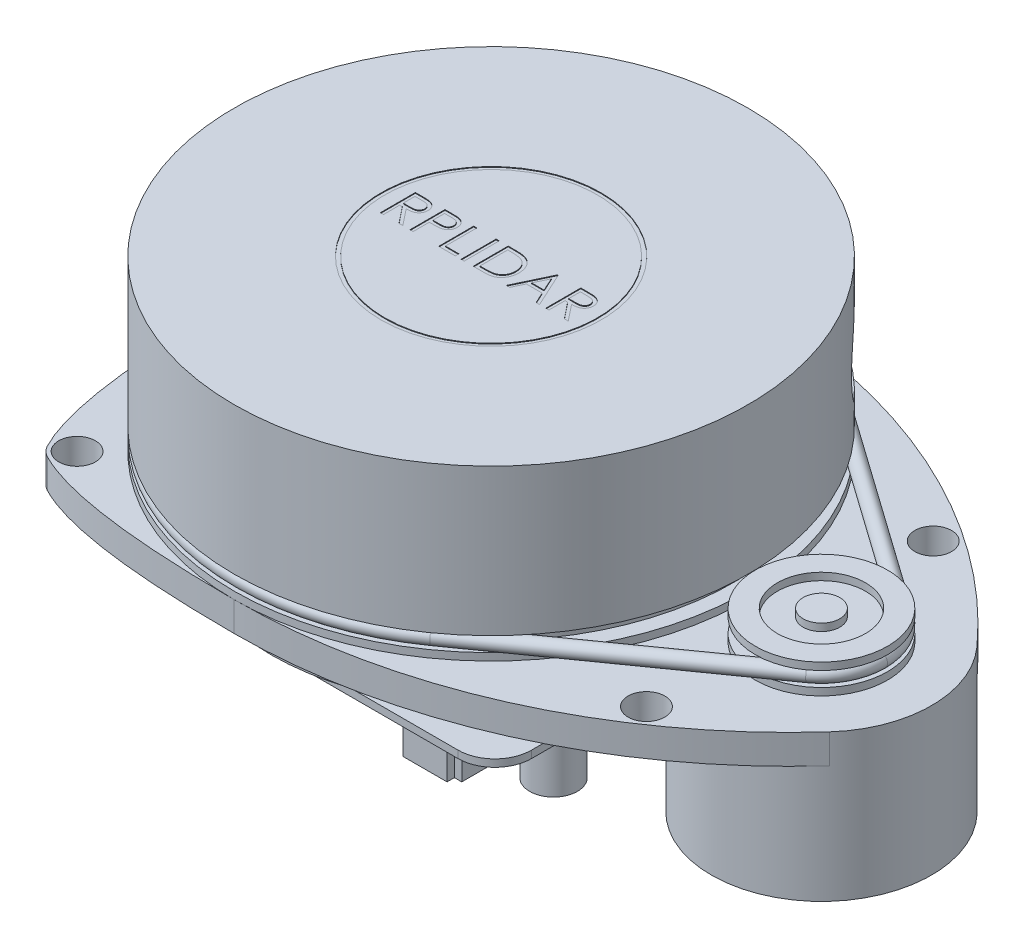
SolidWorks part; units mm, degrees
ref_plane "Front Plane" through (0, 0, 0) normal (0, 0, 1) x (1, 0, 0)
ref_plane "Top Plane" through (0, 0, 0) normal (0, 1, 0) x (1, 0, 0)
ref_plane "Right Plane" through (0, 0, 0) normal (1, 0, 0) x (0, 0, -1)
sketch "Sketch1" plane through (0, 0, 0) normal (0, 0, 1) x (1, 0, 0)
  line L0 (0, 67.5294) -> (0, -49.4672) construction
  line L1 (0, 0) -> (-35, 0)
  line L2 (38.5, 0) -> (-38.5, 0) construction
  line L3 (-35, 0) -> (-35, 1)
  line L4 (-35, 1) -> (-33, 1)
  line L5 (-33, 1) -> (-33, 3)
  line L6 (-33, 3) -> (-35, 3)
  line L7 (-35, 3) -> (-35, 23)
  line L8 (0, 23) -> (0, 0)
  line L9 (-15, 23) -> (-15, 22.9)
  line L10 (-15, 22.9) -> (-14.5, 22.9)
  line L11 (-14.5, 22.9) -> (-14.5, 23)
  line L12 (-35, 23) -> (-15, 23)
  line L13 (-14.5, 23) -> (0, 23)
  dimension "D1" = 1
  dimension "D2" = 2
  dimension "D3" = 2
  dimension "D4" = 35
  dimension "D5" = 2
  dimension "D6" = 23
  dimension "D7" = 0.1
  dimension "D8" = 0.5
  dimension "D9" = 14.5
revolve "Revolve2" add sketch "Sketch1" angle 360 about L0
sketch "Sketch2" plane through (0, 23, 0) normal (0, 1, 0) x (1, 0, 0)
  text T0 "RPLIDAR" font "Century Gothic" height in points 18
  dimension "D1" = 2.3813
extrude "Cut-Extrude2" cut sketch "Sketch2" against normal blind 0.1
sketch "Sketch3" plane through (0, 1, 0) normal (0, 1, 0) x (1, 0, 0)
  line L0 (-51.4402, 0) -> (173.1842, 0) construction
  line L1 (20.2222, 28.5668) -> (50.2, 7.3457)
  line L2 (50.2, -7.3457) -> (20.2222, -28.5668)
  circle A0 centre (0, 0) radius 35 construction
  arc A1 (20.2222, 28.5668) -> (20.2222, -28.5668) centre (0, 0) ccw
  arc A2 (50.2, -7.3457) -> (50.2, 7.3457) centre (45, 0) ccw
  circle A3 centre (0, 0) radius 35 construction
  dimension "D2" = 18
  dimension "D1" = 45
sketch "Sketch4" plane through (0, 0, 0) normal (0, 0, 1) x (1, 0, 0)
  line L0 (54, 2) -> (54, 1) construction
  line L1 (54, 1) -> (50.2, 1) construction
  line L3 (-51.4402, 1) -> (173.1842, 1) construction
  line L4 (54, 2) -> (53, 2) construction
  circle A0 centre (53, 2) radius 1
  point P5 (54, 1)
  dimension "D3" = 2
  dimension "D1" = 1
  dimension "D2" = 1
sweep "Sweep1" add profiles "Sketch4" path "Sketch3"
sketch "Sketch11" plane through (0, 0, 0) normal (0, 1, 0) x (1, 0, 0)
  circle A6 centre (45, 0) radius 9
  arc A7 (54, 0) -> (50.2, 7.3457) centre (45, 0) ccw construction
extrude "Boss-Extrude2" add sketch "Sketch11" along normal blind 1 separate body
sketch "Sketch12" plane through (0, 1, 0) normal (0, 1, 0) x (1, 0, 0)
  circle A0 centre (45, 0) radius 7
  arc A1 (52, 0) -> (49.0444, 5.7134) centre (45, 0) ccw construction
extrude "Boss-Extrude3" add sketch "Sketch12" along normal blind 2
sketch "Sketch13" plane through (0, 3, 0) normal (0, 1, 0) x (1, 0, 0)
  circle A0 centre (45, 0) radius 9
  arc A1 (54, 0) -> (50.2, 7.3457) centre (45, 0) ccw construction
extrude "Boss-Extrude4" add sketch "Sketch13" along normal blind 1
sketch "Sketch14" plane through (0, 4, 0) normal (0, 1, 0) x (1, 0, 0)
  circle A0 centre (45, 0) radius 2.5
  circle A1 centre (45, 0) radius 9 construction
  circle A2 centre (45, 0) radius 6
  dimension "D1" = 5
  dimension "D2" = 12
extrude "Cut-Extrude3" cut sketch "Sketch14" against normal blind 1 contours A2 | A0
sketch "Sketch15" plane through (0, 0, 0) normal (0, 0, 1) x (1, 0, 0)
  line L0 (0, 36.9072) -> (0, -30.0169) construction
  line L1 (13, 17) -> (26, 17)
  line L2 (-54.0593, 12) -> (73.8924, 12) construction
  line L3 (13, 7) -> (26, 7)
  circle A0 centre (-20, 12) radius 4
  arc A5 (13, 17) -> (13, 7) centre (19.5, 12) ccw
  arc A6 (26, 7) -> (26, 17) centre (19.5, 12) ccw
  dimension "D1" = 8
  dimension "D4" = 5
  dimension "D6" = 12
  dimension "D2" = 20
  dimension "D3" = 13
  dimension "D5" = 13
extrude "Cut-Extrude4" cut sketch "Sketch15" against normal through all
sketch "Sketch16" plane through (0, 0, 0) normal (0, -1, 0) x (1, 0, 0)
  line L0 (-102.0481, 0) -> (115.3971, 0) construction
  line L1 (0, -61.7637) -> (0, 138.2935) construction
  line L2 (-30.4056, 30.4056) -> (-30.4056, 0) construction
  line L3 (0, 0) -> (-87.9139, 87.9139) construction
  arc A1 (0, 35) -> (56.134, 10.0515) centre (0, -40.625) cw
  circle A2 centre (0, 0) radius 35 construction
  arc A3 (56.134, -10.0515) -> (56.134, 10.0515) centre (45, 0) ccw
  circle A4 centre (45, 0) radius 9 construction
  arc A5 (0, -35) -> (56.134, -10.0515) centre (0, 40.625) ccw
  spline S0 degree 2 poles (-30.4056, 30.4056) (-22.7272, 35) (0, 35) knots 0 0 0 0.299273 0.299273 0.299273
  spline S1 degree 2 poles (-30.4056, 30.4056) (-35, 22.7272) (-35, 0) knots 0 0 0 0.299273 0.299273 0.299273
  spline S2 degree 2 poles (-30.4056, -30.4056) (-22.7272, -35) (0, -35) knots 0 0 0 0.299273 0.299273 0.299273
  spline S3 degree 2 poles (-30.4056, -30.4056) (-35, -22.7272) (-35, 0) knots 0 0 0 0.299273 0.299273 0.299273
  dimension "D1" = 30
  dimension "D2" = 96.7637
  dimension "D3" = 43
extrude "Boss-Extrude5" add sketch "Sketch16" along normal blind 4
sketch "Sketch18" plane through (0, -4, 0) normal (0, -1, 0) x (1, 0, 0)
  circle A0 centre (45, 0) radius 15
  arc A1 (56.134, -10.0515) -> (56.134, 10.0515) centre (45, 0) ccw construction
extrude "Boss-Extrude7" add sketch "Sketch18" along normal blind 16
sketch "Sketch19" plane through (0, -4, 0) normal (0, -1, 0) x (1, 0, 0)
  line L0 (0, 74.1504) -> (0, -76.1245) construction
  line L1 (-81.9972, 0) -> (97.5204, 0) construction
  arc A0 (29.8306, 3.184) -> (29.8306, -3.184) centre (0, 0) ccw
  arc A1 (29.8306, 3.184) -> (29.8306, -3.184) centre (45, 0) ccw
  circle A2 centre (45, 0) radius 15 construction
  dimension "D1" = 60
  dimension "D2" = 31
extrude "Boss-Extrude11" add sketch "Sketch19" along normal blind 5
sketch "Sketch20" plane through (0, -9, 0) normal (0, -1, 0) x (1, 0, 0)
  line L0 (29, 23.5) -> (29, -23.5)
  line L1 (24, 28.5) -> (-12, 28.5)
  line L2 (-17, 23.5) -> (-17, -23.5)
  line L3 (-12, -28.5) -> (24, -28.5)
  circle A0 centre (45, 0) radius 15 construction
  arc A1 (-17, -23.5) -> (-12, -28.5) centre (-12, -23.5) ccw
  arc A2 (29, -23.5) -> (24, -28.5) centre (24, -23.5) cw
  arc A3 (-12, 28.5) -> (-17, 23.5) centre (-12, 23.5) ccw
  arc A4 (29, 23.5) -> (24, 28.5) centre (24, 23.5) ccw
  point P10 (-17, -28.5)
  point P13 (29, -28.5)
  point P16 (-17, 28.5)
  dimension "D1" = 16
  dimension "D5" = 5
  dimension "D2" = 46
  dimension "D3" = 57
  dimension "D4" = 28.5
extrude "Boss-Extrude12" add sketch "Sketch20" along normal blind 1
fillet "Fillet1" radius 3 2 edges at (-30.4056, -2, 30.4056) (-30.4056, -2, -30.4056)
sketch "Sketch21" plane through (0, 0, 0) normal (0, 1, 0) x (1, 0, 0)
  line L0 (71.416, 2.3686) -> (13.3272, 41.6616) construction
  line L1 (42.3716, 22.0151) -> (40.6908, 19.5302) construction
  line L2 (-44.2011, 0) -> (-49.7046, 0) construction
  circle A0 centre (-28.2001, 28.2001) radius 2.5
  arc A3 (-29.5747, 30.8667) -> (-30.8667, 29.5747) centre (-28.2001, 28.2001) ccw construction
  circle A4 centre (40.6908, 19.5302) radius 2.5
  circle A8 centre (45, 0) radius 2.5
  circle A9 centre (45, 0) radius 2.5 construction
  arc A10 (56.134, 10.0515) -> (0, 35) centre (0, -40.625) ccw construction
  circle A11 centre (-28.2001, -28.2001) radius 2.5
  circle A12 centre (40.6908, -19.5302) radius 2.5
  point P10 (42.3716, 22.0151)
  dimension "D1" = 5
  dimension "D2" = 5
  dimension "D3" = 0
  dimension "D4" = 3
  dimension "D5" = 20
extrude "Cut-Extrude6" cut sketch "Sketch21" against normal blind 10
sketch "Sketch22" plane through (0, -10, 0) normal (0, -1, 0) x (1, 0, 0)
  line L0 (26.5, 32.3083) -> (26.5, -14.2675) construction
  line L5 (29, -23.5) -> (29, 23.5) construction
  line L6 (-12, -28.5) -> (24, -28.5) construction
  line L7 (26.5, -22.5) -> (23, -22.5)
  line L8 (26.5, -22.5) -> (26.5, -14.5)
  line L9 (26.5, -14.5) -> (23, -14.5)
  line L10 (23, -22.5) -> (23, -14.5)
  line L11 (26.5, -12.5) -> (23, -12.5)
  line L12 (23, -12.5) -> (23, -3.5)
  line L13 (23, -3.5) -> (26.5, -3.5)
  line L14 (23, -60.1215) -> (23, -48.2932) construction
  line L15 (26.5, -3.5) -> (26.5, -12.5)
  line L17 (26.5, -1.5) -> (23, -1.5)
  line L18 (26.5, -1.5) -> (26.5, 8.5)
  line L19 (26.5, 8.5) -> (23, 8.5)
  line L20 (23, -1.5) -> (23, 8.5)
  dimension "D1" = 2.5
  dimension "D2" = 3.5
  dimension "D3" = 8
  dimension "D4" = 6
  dimension "D5" = 2
  dimension "D6" = 9
  dimension "D7" = 2
  dimension "D8" = 10
extrude "Boss-Extrude13" add sketch "Sketch22" along normal blind 6.5
sketch "Sketch23" plane through (0, -10, 0) normal (0, -1, 0) x (1, 0, 0)
  line L0 (24, 28.5) -> (-12, 28.5) construction
  line L1 (29, -23.5) -> (29, 23.5) construction
  circle A0 centre (24.75, 16.25) radius 3.25
  dimension "D1" = 6.5
  dimension "D2" = 12.25
  dimension "D3" = 4.25
extrude "Boss-Extrude14" add sketch "Sketch23" along normal blind 8
sketch "Sketch24" plane through (0, -10, 0) normal (0, -1, 0) x (1, 0, 0)
  line L0 (16, 27) -> (16, 28)
  line L1 (16, 28) -> (22, 28)
  line L2 (22, 28) -> (22, 27)
  line L3 (22, 27) -> (23, 27)
  line L4 (23, 27) -> (23, 21)
  line L5 (23, 21) -> (22, 21)
  line L6 (22, 21) -> (22, 20)
  line L7 (22, 20) -> (16, 20)
  line L8 (16, 20) -> (16, 21)
  line L9 (16, 21) -> (15, 21)
  line L10 (15, 21) -> (15, 27)
  line L11 (15, 27) -> (16, 27)
  line L12 (9.3675, 28.5) -> (-9.3675, 28.5) construction
  line L13 (29, -23.5) -> (29, 23.5) construction
  dimension "D1" = 0.5
  dimension "D2" = 6
  dimension "D3" = 1
  dimension "D4" = 6
extrude "Boss-Extrude15" add sketch "Sketch24" along normal blind 4
